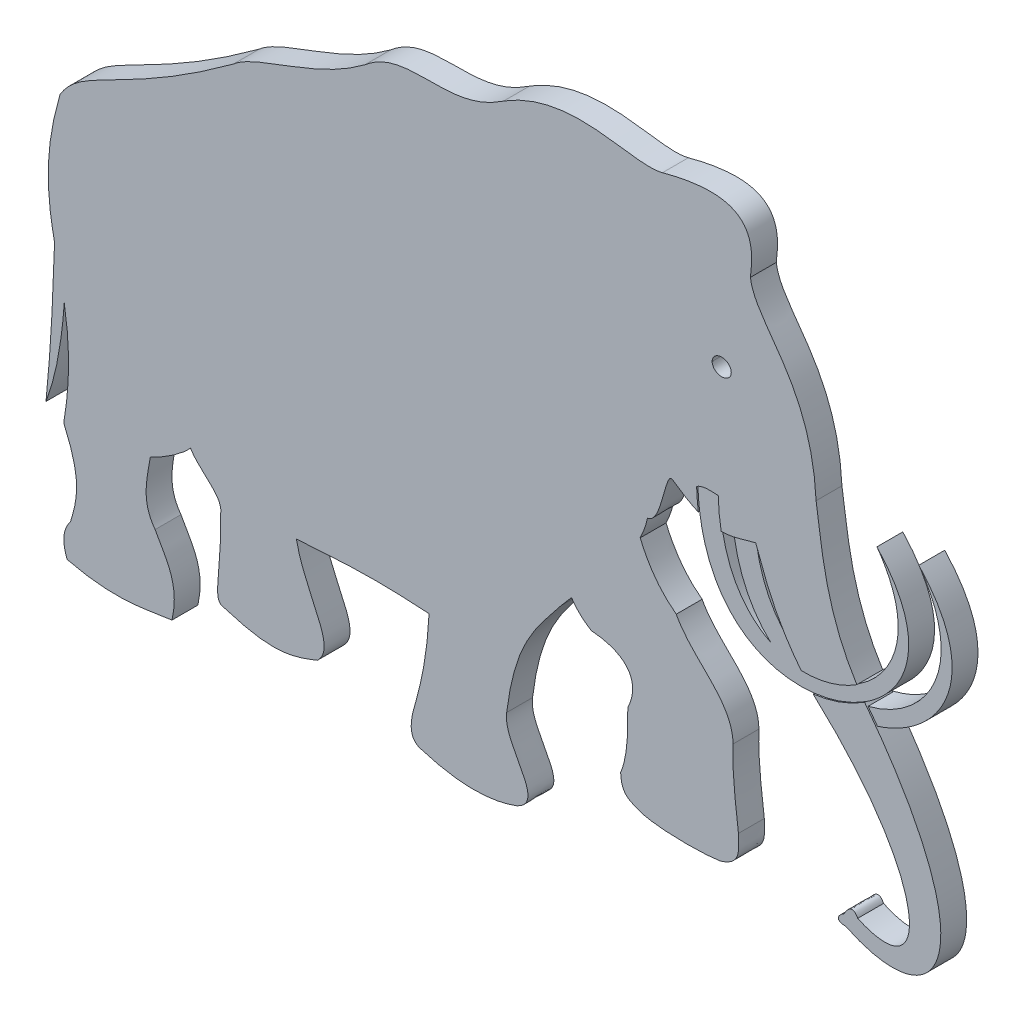
SolidWorks part; units mm, degrees
ref_plane "Plan de face" through (0, 0, 0) normal (0, 0, 1) x (1, 0, 0)
ref_plane "Plan de dessus" through (0, 0, 0) normal (0, 1, 0) x (1, 0, 0)
ref_plane "Plan de droite" through (0, 0, 0) normal (1, 0, 0) x (0, 0, -1)
sketch "Model" plane through (0, 0, 0) normal (0, 0, 1) x (1, 0, 0)
  line L0 (452.3827, -239.3251) -> (398.7526, -314.2399)
  line L1 (15.4936, -260.843) -> (7.6359, -257.2566)
  spline S0 degree 3 poles (398.7526, -314.2399) (405.4257, -323.0056) (407.4173, -331.7727) (421.8688, -340.5398) knots 0 0 0 0 1 1 1 1
  spline S1 degree 3 poles (421.8688, -340.5398) (445.9821, -342.3381) (461.1953, -354.1813) (450.0683, -377.9962) knots 1 1 1 1 2 2 2 2
  spline S2 degree 3 poles (450.0683, -377.9962) (449.7269, -393.4048) (450.7215, -408.8129) (444.522, -424.2201) knots 2 2 2 2 3 3 3 3
  spline S3 degree 3 poles (444.522, -424.2201) (444.8765, -432.7619) (447.048, -438.1342) (455.1543, -440.9567) knots 3 3 3 3 4 4 4 4
  spline S4 degree 3 poles (455.1543, -440.9567) (467.6383, -448.2596) (510.6327, -447.0308) (521.728, -444.941) knots 4 4 4 4 5 5 5 5
  spline S5 degree 3 poles (521.728, -444.941) (538.793, -439.7392) (535.3465, -429.6816) (535.5952, -419.4387) knots 5 5 5 5 6 6 6 6
  spline S6 degree 3 poles (535.5952, -419.4387) (534.0559, -404.8297) (530.5116, -383.7044) (531.4377, -361.6592) knots 6 6 6 6 7 7 7 7
  spline S7 degree 3 poles (531.4377, -361.6592) (530.8978, -333.355) (499.9791, -320.6405) (487.5168, -296.7061) knots 7 7 7 7 8 8 8 8
  spline S8 degree 3 poles (487.5168, -296.7061) (467.9156, -282.1109) (459.6188, -262.3516) (452.3827, -239.3251) knots 8 8 8 8 9 9 9 9
  spline S9 degree 3 poles (674.0853, -171.1053) (777.6821, -281.7881) (535.3599, -380.2969) (529.1074, -200.6289) knots 2 2 2 2 3 3 3 3
  spline S10 degree 3 poles (546.6323, -198.3402) (551.0995, -356.6449) (749.9346, -276.4662) (674.0853, -171.1053) knots 1 1 1 1 2 2 2 2
  spline S11 degree 3 poles (529.1074, -200.6289) (534.4632, -197.3457) (540.5992, -198.1088) (546.6323, -198.3402) knots 0 0 0 0 1 1 1 1
  spline S12 degree 3 poles (7.6359, -257.2566) (6.6282, -304.563) (4.9117, -351.666) (0.2382, -397.9202) knots 0 0 0 0 1 1 1 1
  spline S13 degree 3 poles (0.2382, -397.9202) (14.6792, -360.1465) (16.5728, -308.9069) (15.4936, -260.843) knots 1 1 1 1 2 2 2 2
  spline S14 degree 3 poles (19.1966, -468.9333) (13.6555, -475.8083) (12.267, -484.4731) (16.5835, -495.5966) knots 31 31 31 31 32 32 32 32
  spline S15 degree 3 poles (13.9676, -405.4295) (27.8188, -436.5487) (24.8193, -450.4028) (19.1966, -468.9333) knots 30 30 30 30 31 31 31 31
  spline S16 degree 3 poles (11.0345, -187.0392) (-17.2337, -283.9641) (30.9819, -305.2568) (13.9676, -405.4295) knots 29 29 29 29 30 30 30 30
  spline S17 degree 3 poles (145.1765, -99.5257) (59.0968, -162.7708) (27.4221, -159.525) (11.0345, -187.0392) knots 28 28 28 28 29 29 29 29
  spline S18 degree 3 poles (246.7233, -49.2743) (208.0369, -78.3308) (163.733, -83.4723) (145.1765, -99.5257) knots 27 27 27 27 28 28 28 28
  spline S19 degree 3 poles (353.9488, -19.9704) (311.2475, -49.2339) (279.8608, -21.029) (246.7233, -49.2743) knots 26 26 26 26 27 27 27 27
  spline S20 degree 3 poles (476.8632, -6.4456) (451.8536, -12.988) (406.5261, 13.0793) (353.9488, -19.9704) knots 25 25 25 25 26 26 26 26
  spline S21 degree 3 poles (544.8601, -42.512) (550.0994, -7.9268) (536.3359, 9.5951) (476.8632, -6.4456) knots 24 24 24 24 25 25 25 25
  spline S22 degree 3 poles (595.6336, -166.7051) (591.9942, -90.8591) (548.6315, -71.6657) (544.8601, -42.512) knots 23 23 23 23 24 24 24 24
  spline S23 degree 3 poles (635.42, -285.9688) (602.2006, -242.8014) (600.2831, -195.1846) (595.6336, -166.7051) knots 22 22 22 22 23 23 23 23
  spline S24 degree 3 poles (618.6492, -440.227) (688.5978, -474.2336) (733.3988, -415.6463) (635.42, -285.9688) knots 21 21 21 21 22 22 22 22
  spline S25 degree 3 poles (617.377, -432.3929) (614.1079, -434.031) (608.2998, -439.7382) (618.6492, -440.227) knots 20 20 20 20 21 21 21 21
  spline S26 degree 3 poles (627.8056, -430.2411) (623.8276, -422.4504) (619.1884, -428.6315) (617.377, -432.3929) knots 19 19 19 19 20 20 20 20
  spline S27 degree 3 poles (594.8402, -298.7683) (684.7944, -380.7089) (686.4632, -457.0612) (627.8056, -430.2411) knots 18 18 18 18 19 19 19 19
  spline S28 degree 3 poles (548.9412, -218.1993) (558.7587, -245.6541) (568.1111, -269.5625) (594.8402, -298.7683) knots 17 17 17 17 18 18 18 18
  spline S29 degree 3 poles (484.716, -208.1153) (517.6921, -231.755) (528.4249, -223.2184) (548.9412, -218.1993) knots 16 16 16 16 17 17 17 17
  spline S30 degree 3 poles (465.3211, -243.405) (476.8818, -242.3888) (478.6857, -203.7932) (484.716, -208.1153) knots 15 15 15 15 16 16 16 16
  spline S31 degree 3 poles (398.4063, -335.5513) (415.9787, -313.5233) (458.3307, -277.4728) (465.3211, -243.405) knots 14 14 14 14 15 15 15 15
  spline S32 degree 3 poles (356.4161, -428.0965) (362.9649, -374.1108) (380.8653, -358.4822) (398.4063, -335.5513) knots 13 13 13 13 14 14 14 14
  spline S33 degree 3 poles (364.4091, -486.5801) (388.4986, -475.3205) (353.052, -450.1141) (356.4161, -428.0965) knots 12 12 12 12 13 13 13 13
  spline S34 degree 3 poles (289.967, -485.6468) (317.1639, -494.1735) (342.1419, -495.0502) (364.4091, -486.5801) knots 11 11 11 11 12 12 12 12
  spline S35 degree 3 poles (286.3725, -455.1905) (284.1587, -462.6339) (277.4408, -482.1542) (289.967, -485.6468) knots 10 10 10 10 11 11 11 11
  spline S36 degree 3 poles (296.4122, -391.9048) (295.2354, -415.5826) (292.0404, -434.3886) (286.3725, -455.1905) knots 9 9 9 9 10 10 10 10
  spline S37 degree 3 poles (193.797, -393.2142) (226.453, -391.2485) (247.0142, -388.7491) (296.4122, -391.9048) knots 8 8 8 8 9 9 9 9
  spline S38 degree 3 poles (210.1079, -466.2926) (225.9771, -451.0646) (200.851, -427.7775) (193.797, -393.2142) knots 7 7 7 7 8 8 8 8
  spline S39 degree 3 poles (137.6624, -467.0888) (174.7249, -478.7256) (188.9092, -474.8272) (210.1079, -466.2926) knots 6 6 6 6 7 7 7 7
  spline S40 degree 3 poles (135.3323, -405.0037) (136.5119, -441.931) (127.739, -466.4112) (137.6624, -467.0888) knots 5 5 5 5 6 6 6 6
  spline S41 degree 3 poles (111.8988, -373.1996) (119.6588, -386.1446) (136.7341, -392.8883) (135.3323, -405.0037) knots 4 4 4 4 5 5 5 5
  spline S42 degree 3 poles (80.88, -394.8197) (88.5713, -391.6305) (105.3924, -381.2932) (111.8988, -373.1996) knots 3 3 3 3 4 4 4 4
  spline S43 degree 3 poles (84.5774, -441.4959) (73.3447, -426.468) (78.5632, -409.8472) (80.88, -394.8197) knots 2 2 2 2 3 3 3 3
  spline S44 degree 3 poles (97.6536, -495.5966) (103.7897, -468.5168) (92.4724, -456.4831) (84.5774, -441.4959) knots 1 1 1 1 2 2 2 2
  spline S45 degree 3 poles (16.5835, -495.5966) (53.95, -504.5132) (74.4001, -498.8457) (97.6536, -495.5966) knots 0 0 0 0 1 1 1 1
  spline S46 degree 3 poles (110.9865, -374.1904) (161.72, -400.8334) (173.5481, -394.1892) (195.2491, -393.1667) knots 1 1 1 1 2 2 2 2
  spline S47 degree 3 poles (151.8788, -223.3853) (156.7927, -281.4936) (151.4237, -334.0427) (110.9865, -374.1904) knots 0 0 0 0 1 1 1 1
  spline S48 degree 3 poles (274.854, -340.9377) (276.092, -313.7827) (275.727, -284.5528) (286.4094, -269.6101) knots 1 1 1 1 2 2 2 2
  spline S49 degree 3 poles (296.1187, -391.9423) (295.09, -371.4602) (279.2076, -360.439) (274.854, -340.9377) knots 0 0 0 0 1 1 1 1
  spline S50 degree 3 poles (430.6524, -224.1827) (452.0599, -210.3968) (457.1166, -183.4512) (473.187, -166.801) knots 4 4 4 4 5 5 5 5
  spline S51 degree 3 poles (349.7461, -119.382) (406.6105, -147.0682) (409.9615, -187.727) (430.6524, -224.1827) knots 3 3 3 3 4 4 4 4
  spline S52 degree 3 poles (332.6417, -91.4885) (338.344, -102.9) (344.0464, -118.7907) (349.7461, -119.382) knots 2 2 2 2 3 3 3 3
  spline S53 degree 3 poles (365.9274, -58.0152) (331.9434, -57.1161) (343.7316, -80.3288) (332.6417, -91.4885) knots 1 1 1 1 2 2 2 2
  spline S54 degree 3 poles (470.8729, -48.8509) (443.5381, -39.8213) (429.5758, -60.5377) (365.9274, -58.0152) knots 0 0 0 0 1 1 1 1
  spline S55 degree 3 poles (515.2561, -113.6037) (515.2561, -109.9723) (518.5675, -107.029) (522.651, -107.029) (526.7375, -107.029) (530.0486, -109.9723) (530.0486, -113.6037) knots 2 2 2 2 3 3 3 4 4 4 4
  spline S56 degree 3 poles (530.0486, -113.6037) (530.0486, -117.2352) (526.7375, -120.1785) (522.651, -120.1785) (518.5675, -120.1785) (515.2561, -117.2352) (515.2561, -113.6037) knots 0 0 0 0 1 1 1 2 2 2 2
  spline S57 degree 3 poles (641.6594, -175.0475) (740.5719, -280.725) (509.2047, -374.7819) (503.2351, -203.2358) knots 2 2 2 2 3 3 3 3
  spline S58 degree 3 poles (519.9665, -201.0508) (524.2329, -352.1983) (714.0808, -275.6445) (641.6594, -175.0475) knots 1 1 1 1 2 2 2 2
  spline S59 degree 3 poles (503.2351, -203.2358) (508.3476, -200.101) (514.206, -200.8293) (519.9665, -201.0508) knots 0 0 0 0 1 1 1 1
extrude "Boss.-Extru.1" add sketch "Model" along normal blind 20 contours S57 S59 S58 S29 S9 S11 S10 S28 S23 S22 S21 S20 S19 S18 S17 S16 S12 L1 S13 S15 S14 S45 S44 S43 S42 S46 S47 S41 S38 S37 | S46 S41 S40 S39 S38 | S31 S0 S1 S2 S3 S4 S5 S6 S7 S8 | S0 S31 S8 L0 | S9 S29 S10 S11 | S16 S12 S13 | S12 S16 S13 L1 | S9 S28 S27 S26 S25 S24 | S10 S57 S28 S9 S24 S23 | S23 S57 S10 | S28 S58 S10 region at (431.2275, -283.7996, 0) region at (286.0467, -224.2076, 0) region at (480.4173, -365.8319, 0) region at (538.4024, -209.6886, 0) region at (622.401, -294.0595, 0) region at (655.2452, -370.9666, 0) region at (585.2362, -281.6245, 0) region at (631.5034, -285.0648, 0) region at (169.4822, -433.1094, 0) region at (7.774, -341.6692, 0) region at (11.8131, -284.6487, 0)
sketch "Esquisse7" plane through (0, 0, 0) normal (0, 0, 1) x (1, 0, 0)
  line L0 (452.3827, -239.3251) -> (398.7526, -314.2399)
  line L1 (15.4936, -260.843) -> (7.6359, -257.2566)
  spline S0 degree 3 poles (398.7526, -314.2399) (405.4257, -323.0056) (407.4173, -331.7727) (421.8688, -340.5398) knots 0 0 0 0 1 1 1 1
  spline S1 degree 3 poles (421.8688, -340.5398) (445.9821, -342.3381) (461.1953, -354.1813) (450.0683, -377.9962) knots 1 1 1 1 2 2 2 2
  spline S2 degree 3 poles (450.0683, -377.9962) (449.7269, -393.4048) (450.7215, -408.8129) (444.522, -424.2201) knots 2 2 2 2 3 3 3 3
  spline S3 degree 3 poles (444.522, -424.2201) (444.8765, -432.7619) (447.048, -438.1342) (455.1543, -440.9567) knots 3 3 3 3 4 4 4 4
  spline S4 degree 3 poles (455.1543, -440.9567) (467.6383, -448.2596) (510.6327, -447.0308) (521.728, -444.941) knots 4 4 4 4 5 5 5 5
  spline S5 degree 3 poles (521.728, -444.941) (538.793, -439.7392) (535.3465, -429.6816) (535.5952, -419.4387) knots 5 5 5 5 6 6 6 6
  spline S6 degree 3 poles (535.5952, -419.4387) (534.0559, -404.8297) (530.5116, -383.7044) (531.4377, -361.6592) knots 6 6 6 6 7 7 7 7
  spline S7 degree 3 poles (531.4377, -361.6592) (530.8978, -333.355) (499.9791, -320.6405) (487.5168, -296.7061) knots 7 7 7 7 8 8 8 8
  spline S8 degree 3 poles (487.5168, -296.7061) (467.9156, -282.1109) (459.6188, -262.3516) (452.3827, -239.3251) knots 8 8 8 8 9 9 9 9
  spline S9 degree 3 poles (674.0853, -171.1053) (777.6821, -281.7881) (535.3599, -380.2969) (529.1074, -200.6289) knots 2 2 2 2 3 3 3 3
  spline S10 degree 3 poles (546.6323, -198.3402) (551.0995, -356.6449) (749.9346, -276.4662) (674.0853, -171.1053) knots 1 1 1 1 2 2 2 2
  spline S11 degree 3 poles (529.1074, -200.6289) (534.4632, -197.3457) (540.5992, -198.1088) (546.6323, -198.3402) knots 0 0 0 0 1 1 1 1
  spline S12 degree 3 poles (7.6359, -257.2566) (6.6282, -304.563) (4.9117, -351.666) (0.2382, -397.9202) knots 0 0 0 0 1 1 1 1
  spline S13 degree 3 poles (0.2382, -397.9202) (14.6792, -360.1465) (16.5728, -308.9069) (15.4936, -260.843) knots 1 1 1 1 2 2 2 2
  spline S14 degree 3 poles (19.1966, -468.9333) (13.6555, -475.8083) (12.267, -484.4731) (16.5835, -495.5966) knots 31 31 31 31 32 32 32 32
  spline S15 degree 3 poles (13.9676, -405.4295) (27.8188, -436.5487) (24.8193, -450.4028) (19.1966, -468.9333) knots 30 30 30 30 31 31 31 31
  spline S16 degree 3 poles (11.0345, -187.0392) (-17.2337, -283.9641) (30.9819, -305.2568) (13.9676, -405.4295) knots 29 29 29 29 30 30 30 30
  spline S17 degree 3 poles (145.1765, -99.5257) (59.0968, -162.7708) (27.4221, -159.525) (11.0345, -187.0392) knots 28 28 28 28 29 29 29 29
  spline S18 degree 3 poles (246.7233, -49.2743) (208.0369, -78.3308) (163.733, -83.4723) (145.1765, -99.5257) knots 27 27 27 27 28 28 28 28
  spline S19 degree 3 poles (353.9488, -19.9704) (311.2475, -49.2339) (279.8608, -21.029) (246.7233, -49.2743) knots 26 26 26 26 27 27 27 27
  spline S20 degree 3 poles (476.8632, -6.4456) (451.8536, -12.988) (406.5261, 13.0793) (353.9488, -19.9704) knots 25 25 25 25 26 26 26 26
  spline S21 degree 3 poles (544.8601, -42.512) (550.0994, -7.9268) (536.3359, 9.5951) (476.8632, -6.4456) knots 24 24 24 24 25 25 25 25
  spline S22 degree 3 poles (595.6336, -166.7051) (591.9942, -90.8591) (548.6315, -71.6657) (544.8601, -42.512) knots 23 23 23 23 24 24 24 24
  spline S23 degree 3 poles (635.42, -285.9688) (602.2006, -242.8014) (600.2831, -195.1846) (595.6336, -166.7051) knots 22 22 22 22 23 23 23 23
  spline S24 degree 3 poles (618.6492, -440.227) (688.5978, -474.2336) (733.3988, -415.6463) (635.42, -285.9688) knots 21 21 21 21 22 22 22 22
  spline S25 degree 3 poles (617.377, -432.3929) (614.1079, -434.031) (608.2998, -439.7382) (618.6492, -440.227) knots 20 20 20 20 21 21 21 21
  spline S26 degree 3 poles (627.8056, -430.2411) (623.8276, -422.4504) (619.1884, -428.6315) (617.377, -432.3929) knots 19 19 19 19 20 20 20 20
  spline S27 degree 3 poles (594.8402, -298.7683) (684.7944, -380.7089) (686.4632, -457.0612) (627.8056, -430.2411) knots 18 18 18 18 19 19 19 19
  spline S28 degree 3 poles (548.9412, -218.1993) (558.7587, -245.6541) (568.1111, -269.5625) (594.8402, -298.7683) knots 17 17 17 17 18 18 18 18
  spline S29 degree 3 poles (484.716, -208.1153) (517.6921, -231.755) (528.4249, -223.2184) (548.9412, -218.1993) knots 16 16 16 16 17 17 17 17
  spline S30 degree 3 poles (465.3211, -243.405) (476.8818, -242.3888) (478.6857, -203.7932) (484.716, -208.1153) knots 15 15 15 15 16 16 16 16
  spline S31 degree 3 poles (398.4063, -335.5513) (415.9787, -313.5233) (458.3307, -277.4728) (465.3211, -243.405) knots 14 14 14 14 15 15 15 15
  spline S32 degree 3 poles (356.4161, -428.0965) (362.9649, -374.1108) (380.8653, -358.4822) (398.4063, -335.5513) knots 13 13 13 13 14 14 14 14
  spline S33 degree 3 poles (364.4091, -486.5801) (388.4986, -475.3205) (353.052, -450.1141) (356.4161, -428.0965) knots 12 12 12 12 13 13 13 13
  spline S34 degree 3 poles (289.967, -485.6468) (317.1639, -494.1735) (342.1419, -495.0502) (364.4091, -486.5801) knots 11 11 11 11 12 12 12 12
  spline S35 degree 3 poles (286.3725, -455.1905) (284.1587, -462.6339) (277.4408, -482.1542) (289.967, -485.6468) knots 10 10 10 10 11 11 11 11
  spline S36 degree 3 poles (296.4122, -391.9048) (295.2354, -415.5826) (292.0404, -434.3886) (286.3725, -455.1905) knots 9 9 9 9 10 10 10 10
  spline S37 degree 3 poles (193.797, -393.2142) (226.453, -391.2485) (247.0142, -388.7491) (296.4122, -391.9048) knots 8 8 8 8 9 9 9 9
  spline S38 degree 3 poles (210.1079, -466.2926) (225.9771, -451.0646) (200.851, -427.7775) (193.797, -393.2142) knots 7 7 7 7 8 8 8 8
  spline S39 degree 3 poles (137.6624, -467.0888) (174.7249, -478.7256) (188.9092, -474.8272) (210.1079, -466.2926) knots 6 6 6 6 7 7 7 7
  spline S40 degree 3 poles (135.3323, -405.0037) (136.5119, -441.931) (127.739, -466.4112) (137.6624, -467.0888) knots 5 5 5 5 6 6 6 6
  spline S41 degree 3 poles (111.8988, -373.1996) (119.6588, -386.1446) (136.7341, -392.8883) (135.3323, -405.0037) knots 4 4 4 4 5 5 5 5
  spline S42 degree 3 poles (80.88, -394.8197) (88.5713, -391.6305) (105.3924, -381.2932) (111.8988, -373.1996) knots 3 3 3 3 4 4 4 4
  spline S43 degree 3 poles (84.5774, -441.4959) (73.3447, -426.468) (78.5632, -409.8472) (80.88, -394.8197) knots 2 2 2 2 3 3 3 3
  spline S44 degree 3 poles (97.6536, -495.5966) (103.7897, -468.5168) (92.4724, -456.4831) (84.5774, -441.4959) knots 1 1 1 1 2 2 2 2
  spline S45 degree 3 poles (16.5835, -495.5966) (53.95, -504.5132) (74.4001, -498.8457) (97.6536, -495.5966) knots 0 0 0 0 1 1 1 1
  spline S46 degree 3 poles (110.9865, -374.1904) (161.72, -400.8334) (173.5481, -394.1892) (195.2491, -393.1667) knots 1 1 1 1 2 2 2 2
  spline S47 degree 3 poles (151.8788, -223.3853) (156.7927, -281.4936) (151.4237, -334.0427) (110.9865, -374.1904) knots 0 0 0 0 1 1 1 1
  spline S48 degree 3 poles (274.854, -340.9377) (276.092, -313.7827) (275.727, -284.5528) (286.4094, -269.6101) knots 1 1 1 1 2 2 2 2
  spline S49 degree 3 poles (296.1187, -391.9423) (295.09, -371.4602) (279.2076, -360.439) (274.854, -340.9377) knots 0 0 0 0 1 1 1 1
  spline S50 degree 3 poles (430.6524, -224.1827) (452.0599, -210.3968) (457.1166, -183.4512) (473.187, -166.801) knots 4 4 4 4 5 5 5 5
  spline S51 degree 3 poles (349.7461, -119.382) (406.6105, -147.0682) (409.9615, -187.727) (430.6524, -224.1827) knots 3 3 3 3 4 4 4 4
  spline S52 degree 3 poles (332.6417, -91.4885) (338.344, -102.9) (344.0464, -118.7907) (349.7461, -119.382) knots 2 2 2 2 3 3 3 3
  spline S53 degree 3 poles (365.9274, -58.0152) (331.9434, -57.1161) (343.7316, -80.3288) (332.6417, -91.4885) knots 1 1 1 1 2 2 2 2
  spline S54 degree 3 poles (470.8729, -48.8509) (443.5381, -39.8213) (429.5758, -60.5377) (365.9274, -58.0152) knots 0 0 0 0 1 1 1 1
  spline S55 degree 3 poles (515.2561, -113.6037) (515.2561, -109.9723) (518.5675, -107.029) (522.651, -107.029) (526.7375, -107.029) (530.0486, -109.9723) (530.0486, -113.6037) knots 2 2 2 2 3 3 3 4 4 4 4
  spline S56 degree 3 poles (530.0486, -113.6037) (530.0486, -117.2352) (526.7375, -120.1785) (522.651, -120.1785) (518.5675, -120.1785) (515.2561, -117.2352) (515.2561, -113.6037) knots 0 0 0 0 1 1 1 2 2 2 2
  spline S57 degree 3 poles (641.6594, -175.0475) (740.5719, -280.725) (509.2047, -374.7819) (503.2351, -203.2358) knots 2 2 2 2 3 3 3 3
  spline S58 degree 3 poles (519.9665, -201.0508) (524.2329, -352.1983) (714.0808, -275.6445) (641.6594, -175.0475) knots 1 1 1 1 2 2 2 2
  spline S59 degree 3 poles (503.2351, -203.2358) (508.3476, -200.101) (514.206, -200.8293) (519.9665, -201.0508) knots 0 0 0 0 1 1 1 1
extrude "Boss.-Extru.2" add sketch "Esquisse7" along normal blind 19 contours S58 S29 S57 S9 | S59 S57 S29 S58 | S58 S28 S57 S10 | S58 S9 S57 S28 | S9 S58 S28 S10 S29 | S58 S10 S57 S23 | S58 S23 S57 | S24 S9 S10 S23 region at (512.6958, -211.9729, 0) region at (535.1968, -263.0984, 0) region at (578.841, -289.3122, 0) region at (552.8718, -253.5127, 0) region at (601.7162, -290.4264, 0) region at (639.8996, -289.6249, 0) region at (619.6957, -282.7135, 0) region at (631.0016, -277.924, 0)
sketch "Esquisse9" plane through (0, 0, 0) normal (0, 0, 1) x (1, 0, 0)
  line L0 (452.3827, -239.3251) -> (398.7526, -314.2399)
  line L1 (15.4936, -260.843) -> (7.6359, -257.2566)
  spline S0 degree 3 poles (398.7526, -314.2399) (405.4257, -323.0056) (407.4173, -331.7727) (421.8688, -340.5398) knots 0 0 0 0 1 1 1 1
  spline S1 degree 3 poles (421.8688, -340.5398) (445.9821, -342.3381) (461.1953, -354.1813) (450.0683, -377.9962) knots 1 1 1 1 2 2 2 2
  spline S2 degree 3 poles (450.0683, -377.9962) (449.7269, -393.4048) (450.7215, -408.8129) (444.522, -424.2201) knots 2 2 2 2 3 3 3 3
  spline S3 degree 3 poles (444.522, -424.2201) (444.8765, -432.7619) (447.048, -438.1342) (455.1543, -440.9567) knots 3 3 3 3 4 4 4 4
  spline S4 degree 3 poles (455.1543, -440.9567) (467.6383, -448.2596) (510.6327, -447.0308) (521.728, -444.941) knots 4 4 4 4 5 5 5 5
  spline S5 degree 3 poles (521.728, -444.941) (538.793, -439.7392) (535.3465, -429.6816) (535.5952, -419.4387) knots 5 5 5 5 6 6 6 6
  spline S6 degree 3 poles (535.5952, -419.4387) (534.0559, -404.8297) (530.5116, -383.7044) (531.4377, -361.6592) knots 6 6 6 6 7 7 7 7
  spline S7 degree 3 poles (531.4377, -361.6592) (530.8978, -333.355) (499.9791, -320.6405) (487.5168, -296.7061) knots 7 7 7 7 8 8 8 8
  spline S8 degree 3 poles (487.5168, -296.7061) (467.9156, -282.1109) (459.6188, -262.3516) (452.3827, -239.3251) knots 8 8 8 8 9 9 9 9
  spline S9 degree 3 poles (674.0853, -171.1053) (777.6821, -281.7881) (535.3599, -380.2969) (529.1074, -200.6289) knots 2 2 2 2 3 3 3 3
  spline S10 degree 3 poles (546.6323, -198.3402) (551.0995, -356.6449) (749.9346, -276.4662) (674.0853, -171.1053) knots 1 1 1 1 2 2 2 2
  spline S11 degree 3 poles (529.1074, -200.6289) (534.4632, -197.3457) (540.5992, -198.1088) (546.6323, -198.3402) knots 0 0 0 0 1 1 1 1
  spline S12 degree 3 poles (7.6359, -257.2566) (6.6282, -304.563) (4.9117, -351.666) (0.2382, -397.9202) knots 0 0 0 0 1 1 1 1
  spline S13 degree 3 poles (0.2382, -397.9202) (14.6792, -360.1465) (16.5728, -308.9069) (15.4936, -260.843) knots 1 1 1 1 2 2 2 2
  spline S14 degree 3 poles (19.1966, -468.9333) (13.6555, -475.8083) (12.267, -484.4731) (16.5835, -495.5966) knots 31 31 31 31 32 32 32 32
  spline S15 degree 3 poles (13.9676, -405.4295) (27.8188, -436.5487) (24.8193, -450.4028) (19.1966, -468.9333) knots 30 30 30 30 31 31 31 31
  spline S16 degree 3 poles (11.0345, -187.0392) (-17.2337, -283.9641) (30.9819, -305.2568) (13.9676, -405.4295) knots 29 29 29 29 30 30 30 30
  spline S17 degree 3 poles (145.1765, -99.5257) (59.0968, -162.7708) (27.4221, -159.525) (11.0345, -187.0392) knots 28 28 28 28 29 29 29 29
  spline S18 degree 3 poles (246.7233, -49.2743) (208.0369, -78.3308) (163.733, -83.4723) (145.1765, -99.5257) knots 27 27 27 27 28 28 28 28
  spline S19 degree 3 poles (353.9488, -19.9704) (311.2475, -49.2339) (279.8608, -21.029) (246.7233, -49.2743) knots 26 26 26 26 27 27 27 27
  spline S20 degree 3 poles (476.8632, -6.4456) (451.8536, -12.988) (406.5261, 13.0793) (353.9488, -19.9704) knots 25 25 25 25 26 26 26 26
  spline S21 degree 3 poles (544.8601, -42.512) (550.0994, -7.9268) (536.3359, 9.5951) (476.8632, -6.4456) knots 24 24 24 24 25 25 25 25
  spline S22 degree 3 poles (595.6336, -166.7051) (591.9942, -90.8591) (548.6315, -71.6657) (544.8601, -42.512) knots 23 23 23 23 24 24 24 24
  spline S23 degree 3 poles (635.42, -285.9688) (602.2006, -242.8014) (600.2831, -195.1846) (595.6336, -166.7051) knots 22 22 22 22 23 23 23 23
  spline S24 degree 3 poles (618.6492, -440.227) (688.5978, -474.2336) (733.3988, -415.6463) (635.42, -285.9688) knots 21 21 21 21 22 22 22 22
  spline S25 degree 3 poles (617.377, -432.3929) (614.1079, -434.031) (608.2998, -439.7382) (618.6492, -440.227) knots 20 20 20 20 21 21 21 21
  spline S26 degree 3 poles (627.8056, -430.2411) (623.8276, -422.4504) (619.1884, -428.6315) (617.377, -432.3929) knots 19 19 19 19 20 20 20 20
  spline S27 degree 3 poles (594.8402, -298.7683) (684.7944, -380.7089) (686.4632, -457.0612) (627.8056, -430.2411) knots 18 18 18 18 19 19 19 19
  spline S28 degree 3 poles (548.9412, -218.1993) (558.7587, -245.6541) (568.1111, -269.5625) (594.8402, -298.7683) knots 17 17 17 17 18 18 18 18
  spline S29 degree 3 poles (484.716, -208.1153) (517.6921, -231.755) (528.4249, -223.2184) (548.9412, -218.1993) knots 16 16 16 16 17 17 17 17
  spline S30 degree 3 poles (465.3211, -243.405) (476.8818, -242.3888) (478.6857, -203.7932) (484.716, -208.1153) knots 15 15 15 15 16 16 16 16
  spline S31 degree 3 poles (398.4063, -335.5513) (415.9787, -313.5233) (458.3307, -277.4728) (465.3211, -243.405) knots 14 14 14 14 15 15 15 15
  spline S32 degree 3 poles (356.4161, -428.0965) (362.9649, -374.1108) (380.8653, -358.4822) (398.4063, -335.5513) knots 13 13 13 13 14 14 14 14
  spline S33 degree 3 poles (364.4091, -486.5801) (388.4986, -475.3205) (353.052, -450.1141) (356.4161, -428.0965) knots 12 12 12 12 13 13 13 13
  spline S34 degree 3 poles (289.967, -485.6468) (317.1639, -494.1735) (342.1419, -495.0502) (364.4091, -486.5801) knots 11 11 11 11 12 12 12 12
  spline S35 degree 3 poles (286.3725, -455.1905) (284.1587, -462.6339) (277.4408, -482.1542) (289.967, -485.6468) knots 10 10 10 10 11 11 11 11
  spline S36 degree 3 poles (296.4122, -391.9048) (295.2354, -415.5826) (292.0404, -434.3886) (286.3725, -455.1905) knots 9 9 9 9 10 10 10 10
  spline S37 degree 3 poles (193.797, -393.2142) (226.453, -391.2485) (247.0142, -388.7491) (296.4122, -391.9048) knots 8 8 8 8 9 9 9 9
  spline S38 degree 3 poles (210.1079, -466.2926) (225.9771, -451.0646) (200.851, -427.7775) (193.797, -393.2142) knots 7 7 7 7 8 8 8 8
  spline S39 degree 3 poles (137.6624, -467.0888) (174.7249, -478.7256) (188.9092, -474.8272) (210.1079, -466.2926) knots 6 6 6 6 7 7 7 7
  spline S40 degree 3 poles (135.3323, -405.0037) (136.5119, -441.931) (127.739, -466.4112) (137.6624, -467.0888) knots 5 5 5 5 6 6 6 6
  spline S41 degree 3 poles (111.8988, -373.1996) (119.6588, -386.1446) (136.7341, -392.8883) (135.3323, -405.0037) knots 4 4 4 4 5 5 5 5
  spline S42 degree 3 poles (80.88, -394.8197) (88.5713, -391.6305) (105.3924, -381.2932) (111.8988, -373.1996) knots 3 3 3 3 4 4 4 4
  spline S43 degree 3 poles (84.5774, -441.4959) (73.3447, -426.468) (78.5632, -409.8472) (80.88, -394.8197) knots 2 2 2 2 3 3 3 3
  spline S44 degree 3 poles (97.6536, -495.5966) (103.7897, -468.5168) (92.4724, -456.4831) (84.5774, -441.4959) knots 1 1 1 1 2 2 2 2
  spline S45 degree 3 poles (16.5835, -495.5966) (53.95, -504.5132) (74.4001, -498.8457) (97.6536, -495.5966) knots 0 0 0 0 1 1 1 1
  spline S46 degree 3 poles (110.9865, -374.1904) (161.72, -400.8334) (173.5481, -394.1892) (195.2491, -393.1667) knots 1 1 1 1 2 2 2 2
  spline S47 degree 3 poles (151.8788, -223.3853) (156.7927, -281.4936) (151.4237, -334.0427) (110.9865, -374.1904) knots 0 0 0 0 1 1 1 1
  spline S48 degree 3 poles (274.854, -340.9377) (276.092, -313.7827) (275.727, -284.5528) (286.4094, -269.6101) knots 1 1 1 1 2 2 2 2
  spline S49 degree 3 poles (296.1187, -391.9423) (295.09, -371.4602) (279.2076, -360.439) (274.854, -340.9377) knots 0 0 0 0 1 1 1 1
  spline S50 degree 3 poles (430.6524, -224.1827) (452.0599, -210.3968) (457.1166, -183.4512) (473.187, -166.801) knots 4 4 4 4 5 5 5 5
  spline S51 degree 3 poles (349.7461, -119.382) (406.6105, -147.0682) (409.9615, -187.727) (430.6524, -224.1827) knots 3 3 3 3 4 4 4 4
  spline S52 degree 3 poles (332.6417, -91.4885) (338.344, -102.9) (344.0464, -118.7907) (349.7461, -119.382) knots 2 2 2 2 3 3 3 3
  spline S53 degree 3 poles (365.9274, -58.0152) (331.9434, -57.1161) (343.7316, -80.3288) (332.6417, -91.4885) knots 1 1 1 1 2 2 2 2
  spline S54 degree 3 poles (470.8729, -48.8509) (443.5381, -39.8213) (429.5758, -60.5377) (365.9274, -58.0152) knots 0 0 0 0 1 1 1 1
  spline S55 degree 3 poles (515.2561, -113.6037) (515.2561, -109.9723) (518.5675, -107.029) (522.651, -107.029) (526.7375, -107.029) (530.0486, -109.9723) (530.0486, -113.6037) knots 2 2 2 2 3 3 3 4 4 4 4
  spline S56 degree 3 poles (530.0486, -113.6037) (530.0486, -117.2352) (526.7375, -120.1785) (522.651, -120.1785) (518.5675, -120.1785) (515.2561, -117.2352) (515.2561, -113.6037) knots 0 0 0 0 1 1 1 2 2 2 2
  spline S57 degree 3 poles (641.6594, -175.0475) (740.5719, -280.725) (509.2047, -374.7819) (503.2351, -203.2358) knots 2 2 2 2 3 3 3 3
  spline S58 degree 3 poles (519.9665, -201.0508) (524.2329, -352.1983) (714.0808, -275.6445) (641.6594, -175.0475) knots 1 1 1 1 2 2 2 2
  spline S59 degree 3 poles (503.2351, -203.2358) (508.3476, -200.101) (514.206, -200.8293) (519.9665, -201.0508) knots 0 0 0 0 1 1 1 1
extrude "Boss.-Extru.3" add sketch "Esquisse9" against normal blind 1 contours S9 S29 S10 S11 | S9 S58 S28 S10 S29 | S28 S58 S10 | S58 S9 S57 S28 | S58 S29 S57 S9 | S58 S28 S57 S10 | S10 S57 S28 S9 S24 S23 | S24 S9 S10 S23 | S58 S23 S57 region at (535.1968, -263.0984, 0) region at (578.841, -289.3122, 0) region at (552.8718, -253.5127, 0) region at (538.4024, -209.6886, 0) region at (622.401, -294.0595, 0) region at (601.7162, -290.4264, 0) region at (585.2362, -281.6245, 0) region at (639.8996, -289.6249, 0) region at (631.0016, -277.924, 0)
